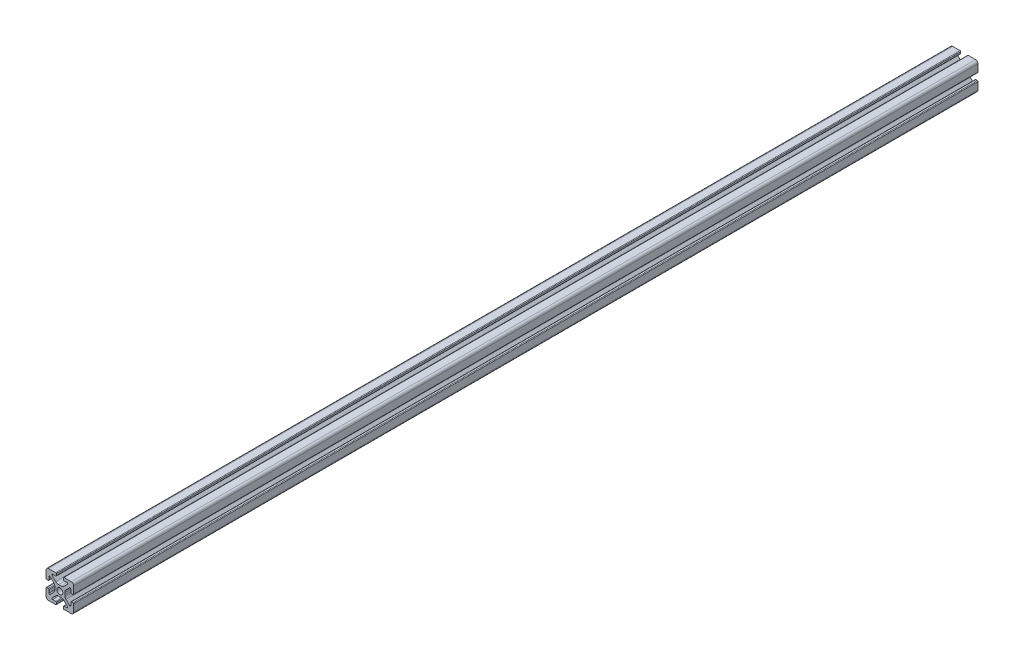
SolidWorks part; units mm, degrees
ref_plane "Front Plane" through (0, 0, 0) normal (0, 0, 1) x (1, 0, 0)
ref_plane "Top Plane" through (0, 0, 0) normal (0, 1, 0) x (1, 0, 0)
ref_plane "Right Plane" through (0, 0, 0) normal (1, 0, 0) x (0, 0, -1)
sketch "Sketch2" plane through (0, 0, 0) normal (0, 0, 1) x (1, 0, 0)
  line L0 (0, 10) -> (0, -10) construction
  line L1 (-10, 0) -> (10, 0) construction
  line L2 (2.5, -10) -> (10, -10)
  line L3 (10, -10) -> (10, -2.5)
  line L4 (2.5, -10) -> (2.5, -7.9246)
  line L5 (2.5, -7.9246) -> (6.4571, -7.9246)
  line L6 (6.4571, -7.9246) -> (2.1325, -3.6)
  line L7 (0, 0) -> (10, -10) construction
  line L8 (10, -2.5) -> (7.9246, -2.5)
  line L9 (7.9246, -2.5) -> (7.9246, -6.4571)
  line L10 (7.9246, -6.4571) -> (3.6, -2.1325)
  line L11 (5.7623, -4.2948) -> (4.2948, -5.7623) construction
  circle A0 centre (0, 0) radius 2.15
  arc A1 (5.25, -7.9246) -> (5.6036, -7.0711) centre (5.25, -7.4246) ccw construction
  point P8 (0, -3.6)
  point P16 (5.0286, -5.0286)
  dimension "Center Hole Diameter" = 4.3
  dimension "D3" = 0.5
  dimension "Rail Height" = 20
  dimension "Rail Width" = 20
  dimension "T-Slot Width" = 5
  dimension "Slot Depth" = 6.4
  dimension "Slot Inner Width" = 11.5
sketch "Sketch3" plane through (0, 0, 0) normal (1, 0, 0) x (0, 0, -1)
  line L0 (-152.4, -10) -> (152.4, -10) construction
  line L1 (-127, 0) -> (127, 0) construction
  line L2 (0, 10) -> (0, -10) construction
  line L3 (0, 10) -> (0, -10) construction
  point P6 (-127, 0)
  point P8 (127, 0)
  dimension "Length" = 304.8
  dimension "D1" = 25.4
sketch "Sketch4" plane through (0, 0, 0) normal (0, 0, 1) x (1, 0, 0)
  line L0 (3, -10) -> (8.25, -10)
  line L1 (2.5, -10) -> (10, -10) construction
  line L2 (2.5, -10) -> (2.5, -7.9246) construction
  line L3 (2.5, -7.9246) -> (6.4571, -7.9246) construction
  line L4 (2.5, -8.4246) -> (2.5, -9.5)
  line L5 (3, -7.9246) -> (5.25, -7.9246)
  line L6 (0, -3.6) -> (0.8898, -3.6)
  line L7 (6.4571, -7.9246) -> (2.1325, -3.6) construction
  line L8 (3.0112, -4.4787) -> (5.6036, -7.0711)
  line L9 (10, -10) -> (10, -2.5) construction
  line L10 (7.9246, -6.4571) -> (3.6, -2.1325) construction
  line L11 (7.9246, -2.5) -> (7.9246, -6.4571) construction
  line L12 (7.9246, -5.25) -> (7.9246, -3)
  line L13 (10, -2.5) -> (7.9246, -2.5) construction
  line L14 (8.4246, -2.5) -> (9.5, -2.5)
  line L15 (10, -3) -> (10, -8.25)
  line L16 (7.0711, -5.6036) -> (4.4787, -3.0112)
  line L17 (3.6, 0) -> (3.6, -0.8898)
  line L18 (-10, 0) -> (10, 0) construction
  line L19 (0, -3.6) -> (0, -2.15)
  line L20 (0, 10) -> (0, -10) construction
  line L21 (3.6, 0) -> (2.15, 0)
  arc A0 (2.5, -9.5) -> (3, -10) centre (3, -9.5) ccw
  arc A1 (5.25, -7.9246) -> (5.6036, -7.0711) centre (5.25, -7.4246) ccw construction
  arc A2 (2.5, -8.4246) -> (3, -7.9246) centre (3, -8.4246) cw
  arc A3 (5.25, -7.9246) -> (5.6036, -7.0711) centre (5.25, -7.4246) ccw
  arc A4 (0.8898, -3.6) -> (3.0112, -4.4787) centre (0.8898, -6.6) cw
  arc A5 (8.25, -10) -> (10, -8.25) centre (8.25, -8.25) ccw
  arc A6 (7.0711, -5.6036) -> (7.9246, -5.25) centre (7.4246, -5.25) ccw
  arc A7 (7.9246, -3) -> (8.4246, -2.5) centre (8.4246, -3) cw
  arc A8 (9.5, -2.5) -> (10, -3) centre (9.5, -3) cw
  arc A9 (4.4787, -3.0112) -> (3.6, -0.8898) centre (6.6, -0.8898) cw
  circle A10 centre (0, 0) radius 2.15 construction
  arc A11 (0, -2.15) -> (2.15, 0) centre (0, 0) ccw
  dimension "D1" = 1.75
  dimension "D2" = 3
extrude "Boss-Extrude1" add sketch "Sketch4" along normal mid plane 654.5
mirror "Mirror1" about plane through (0, 0, 0) normal (1, 0, 0) of bodies 134
mirror "Mirror2" about plane through (0, 0, 0) normal (0, 1, 0) of bodies 135
equation "\"D3@Sketch2\"=\"T-Slot Width@Sketch2\"*0.1"
equation "\"D1@Sketch4\"=\"D3@Sketch2\"*3.5"
equation "\"D2@Sketch4\"=\"D3@Sketch2\"*6"
equation "\"D1@Boss-Extrude1\"=\"Length@Sketch3\""
